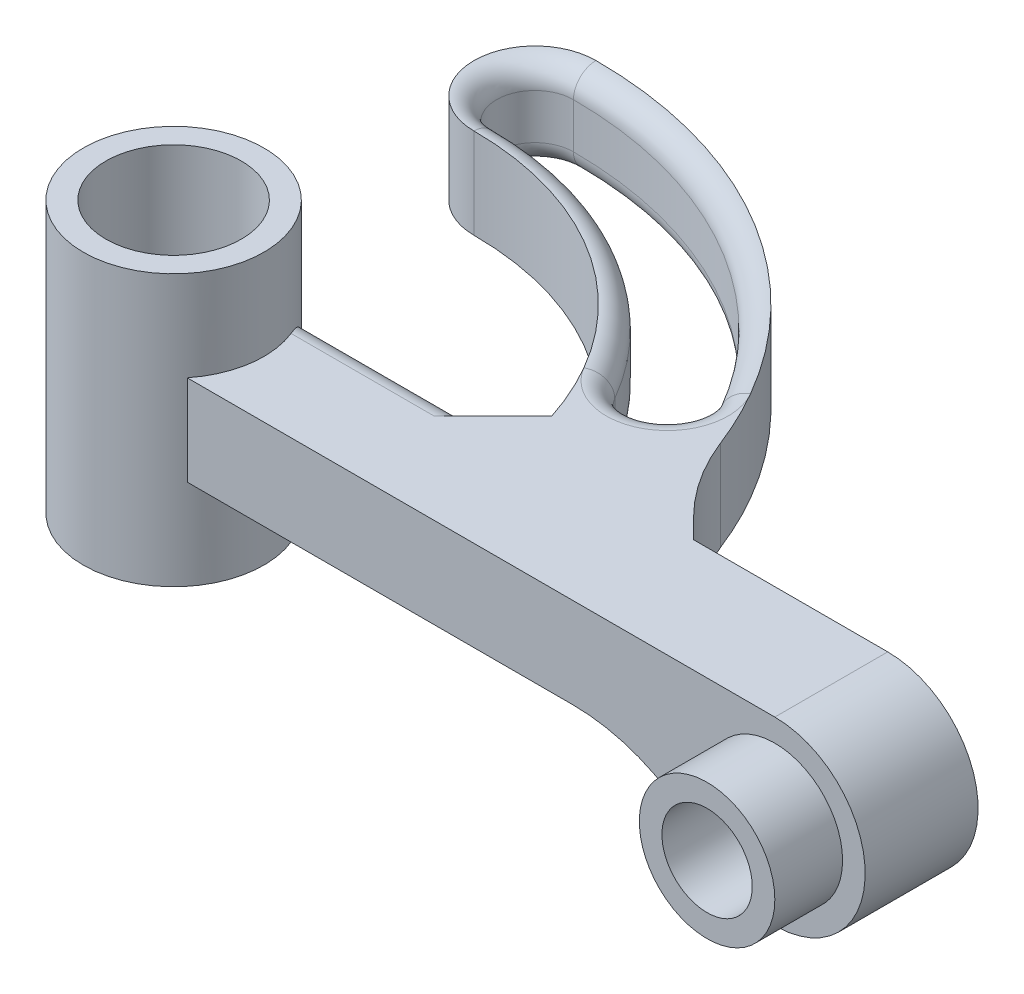
SolidWorks part; units mm, degrees
ref_plane "前视基准面" through (0, 0, 0) normal (0, 0, 1) x (1, 0, 0)
ref_plane "上视基准面" through (0, 0, 0) normal (0, 1, 0) x (1, 0, 0)
ref_plane "右视基准面" through (0, 0, 0) normal (1, 0, 0) x (0, 0, -1)
other "Configuration Table"
sketch "草图3" plane through (0, 0, 0) normal (0, 0, 1) x (1, 0, 0)
  line L0 (0, 0) -> (17.0557, 0)
  line L2 (26, 4) -> (0, 4)
  line L3 (0, 4) -> (0, 0)
  arc A0 (23.0186, -2.6667) -> (26, 4) centre (26, 0) ccw
  arc A1 (23.0186, -2.6667) -> (17.0557, 0) centre (17.0557, -8) ccw
  circle A2 centre (26, 0) radius 3
  circle A3 centre (26, 0) radius 2
  point P11 (0, 0)
  dimension "D2" = 8
  dimension "D3" = 8
  dimension "D4" = 4
  dimension "D6" = 1
  dimension "D1" = 26
  dimension "D5" = 1
extrude "凸台-拉伸5" add sketch "草图3" along normal blind 5 contours A1 A0 L2 L3 L0 A2 region at (14.4419, 1.5869, 0)
extrude "凸台-拉伸6" add sketch "草图3<3>" along normal blind 8 contours A2 A3 region at (23.0849, 0, 0)
sketch "草图3<3>" plane through (0, 0, 0) normal (0, 0, 1) x (1, 0, 0) same geometry as "草图3"
sketch "草图6" plane through (0, 0, 0) normal (0, 1, 0) x (1, 0, 0)
  circle A0 centre (-3.1337, -2.4859) radius 4
  circle A1 centre (-3.1337, -2.4859) radius 3
  point P2 (0, 0)
  point P3 (0, 0)
  dimension "D2" = 8
  dimension "D1" = 2.4859
  dimension "D3" = 1
extrude "凸台-拉伸8" add sketch "草图6" along normal blind 8 and the other way blind 4 contours A0 | A1
sketch "草图7" plane through (0, 0, 0) normal (0, 1, 0) x (1, 0, 0)
  line L0 (9.9307, -0.002) -> (15.4022, -0.0028)
  line L1 (-3.1337, -2.4859) -> (-3.1337, 13.5141) construction
  line L2 (-3.1337, -2.4859) -> (10.7227, 5.5141) construction
  arc A0 (10.7227, 5.5141) -> (-3.1337, 13.5141) centre (-3.1337, -2.4859) ccw construction
  arc A1 (12.1962, 6.3648) -> (-3.1337, 15.2156) centre (-3.1337, -2.4859) ccw
  arc A2 (9.2491, 4.6633) -> (-3.1337, 11.8126) centre (-3.1337, -2.4859) ccw
  arc A3 (9.2491, 4.6633) -> (12.1962, 6.3648) centre (10.7227, 5.5141) ccw
  arc A4 (-3.1337, 15.2156) -> (-3.1337, 11.8126) centre (-3.1337, 13.5141) ccw
  arc A5 (15.4022, -0.0028) -> (-3.1337, 16.2156) centre (-3.1337, -2.4859) ccw
  arc A6 (-3.1337, 16.2156) -> (-3.1337, 10.8126) centre (-3.1337, 13.5141) ccw
  arc A7 (9.9307, -0.002) -> (-3.1337, 10.8126) centre (-3.1337, -2.4859) ccw
  arc A9 (8.3831, 4.1633) -> (13.0623, 6.8648) centre (10.7227, 5.5141) ccw construction
  arc A10 (8.3831, 4.1633) -> (-3.1337, 10.8126) centre (-3.1337, -2.4859) ccw construction
  arc A11 (13.0623, 6.8648) -> (-3.1337, 16.2156) centre (-3.1337, -2.4859) ccw construction
  point P4 (4.8663, 11.3705)
  point P20 (0, 0)
  point P21 (0, 0)
  point P22 (0, 0)
  dimension "D4" = 5.4715
  dimension "D5" = 1.7015
  dimension "D6" = 5.5162
  dimension "D1" = 60
  dimension "D2" = 16
  dimension "D3" = 1
extrude "凸台-拉伸9" add sketch "草图7" along normal blind 4
chamfer "倒角1" distance 2 angle 45 2 edges at (9.9303, 2, 0) (15.4018, 2, 0) first distance on face at (4.9652, 2, 0) first distance on face at (28, 0, 0)
fillet "圆角1" radius 10 1 edges at (14.8867, 2, -2.5151)
fillet "圆角2" radius 1 10 edges at (-4.8352, 0, -13.5141) (5.717, 0, -12.8441) (11.5734, 0, -4.0405) (-4.8352, 4, -13.5141) (5.717, 4, -12.8441) (11.5734, 4, -4.0405) (4.0155, 0, -9.8969) (4.0155, 4, -9.8969) (3.9652, 0, 0) (3.9652, 4, 0)
